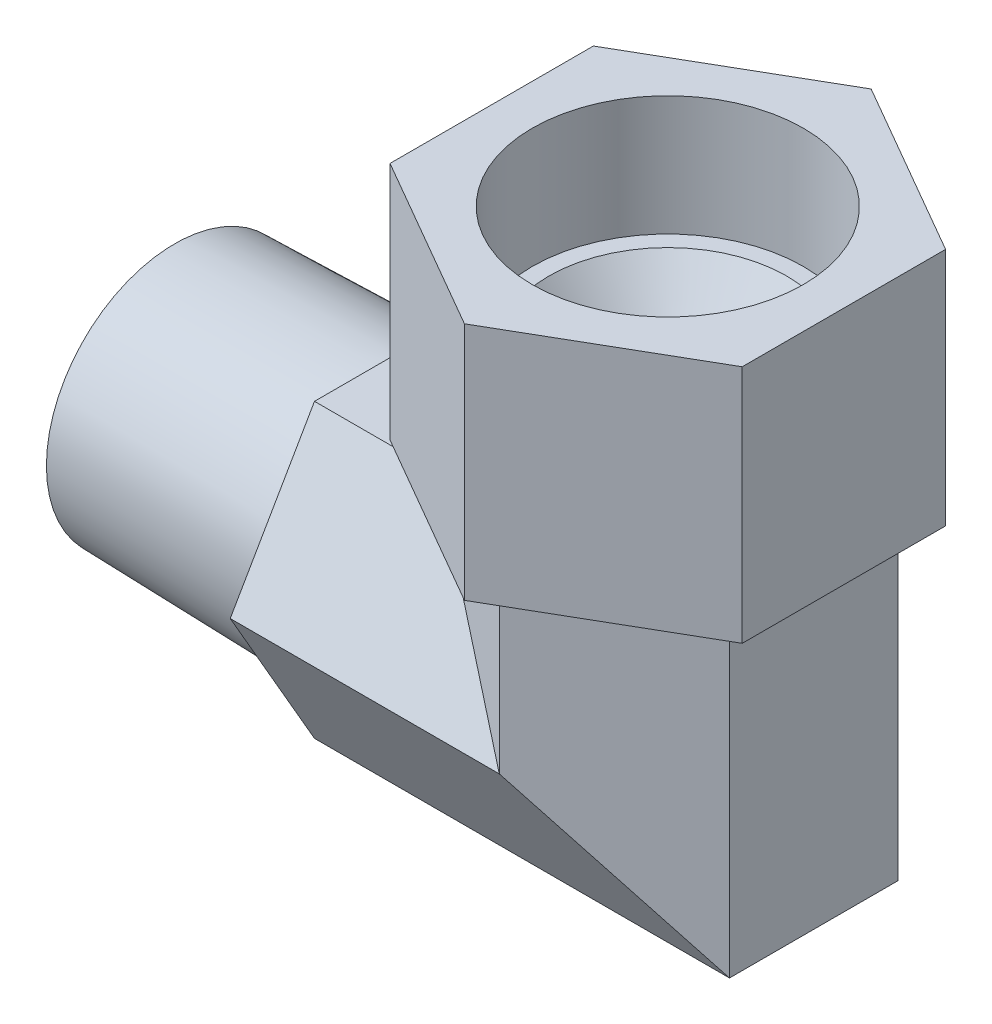
SolidWorks part; units mm, degrees
material "2024-T3"
ref_plane "Front Plane" through (0, 0, 0) normal (0, 0, 1) x (1, 0, 0)
ref_plane "Top Plane" through (0, 0, 0) normal (0, 1, 0) x (1, 0, 0)
ref_plane "Right Plane" through (0, 0, 0) normal (1, 0, 0) x (0, 0, -1)
sketch "Sketch1" plane through (0, 0, 0) normal (0, 0, 1) x (1, 0, 0)
  line L0 (0, 0) -> (33.9096, 0) construction
  line L7 (0, 0) -> (44.45, 0)
  line L8 (44.45, 0) -> (44.45, 25.908)
  dimension "D1" = 44.45
  dimension "D2" = 25.908
ref_plane "Plane1" through (0, 0, 0) normal (1, 0, 0) x (0, 0, -1)
sketch "Sketch2" plane through (0, 0, 0) normal (1, 0, 0) x (0, 0, -1)
  line L0 (0, 0) -> (27.4531, 0) construction
  line L1 (7.5963, 13.1572) -> (-7.5963, 13.1572)
  line L2 (-7.5963, 13.1572) -> (-15.1926, 0)
  line L3 (-15.1926, 0) -> (-7.5963, -13.1572)
  line L4 (-7.5963, -13.1572) -> (7.5963, -13.1572)
  line L5 (7.5963, -13.1572) -> (15.1926, 0)
  line L6 (15.1926, 0) -> (7.5963, 13.1572)
  circle A0 centre (0, 0) radius 13.1572 construction
  dimension "D1" = 26.3144
sweep "Sweep1" add profiles "Sketch2" path "Sketch1"
sketch "Sketch3" plane through (0, 0, 0) normal (-1, 0, 0) x (0, 0, 1)
  circle A0 centre (0, 0) radius 9.1313
  dimension "D1" = 18.2626
extrude "Cut-Extrude1" cut sketch "Sketch3" against normal blind 52.1843
sketch "Sketch4" plane through (0, 25.908, 0) normal (0, 1, 0) x (1, 0, 0)
  line L0 (0, 0) -> (44.45, 0) construction
  line L1 (44.45, 15.1926) -> (44.45, -15.1926) construction
  line L2 (44.45, -15.1926) -> (31.2928, -7.5963) construction
  line L3 (0, -15.1926) -> (44.45, -15.1926) construction
  line L4 (57.6072, 0) -> (31.2928, 0) construction
  line L5 (57.6072, -7.5963) -> (57.6072, 7.5963) construction
  line L6 (31.2928, 7.5963) -> (31.2928, -7.5963) construction
  circle A0 centre (44.45, 0) radius 7.7343
  dimension "D1" = 15.4686
extrude "Cut-Extrude2" cut sketch "Sketch4" against normal blind 25.908
chamfer "Chamfer1" distance 3.9624 angle 37 1 edges at (36.7157, 25.908, 0) first distance on face at (36.7157, 25.908, 0)
sketch "Sketch5" plane through (0, 0, 0) normal (-1, 0, 0) x (0, 0, 1)
  line L6 (-7.5963, 13.1572) -> (-15.1926, 0)
  line L7 (-15.1926, 0) -> (-7.5963, -13.1572)
  line L8 (-7.5963, -13.1572) -> (7.5963, -13.1572)
  line L9 (7.5963, -13.1572) -> (15.1926, 0)
  line L10 (15.1926, 0) -> (7.5963, 13.1572)
  line L11 (7.5963, 13.1572) -> (-7.5963, 13.1572)
  line L12 (-7.5963, 13.1572) -> (-15.1926, 0)
  line L13 (-15.1926, 0) -> (-7.5963, -13.1572)
  line L14 (-7.5963, -13.1572) -> (7.5963, -13.1572)
  line L15 (7.5963, -13.1572) -> (15.1926, 0)
  line L16 (15.1926, 0) -> (7.5963, 13.1572)
  line L17 (7.5963, 13.1572) -> (-7.5963, 13.1572)
  circle A0 centre (0, 0) radius 11.5633
  dimension "D2" = 23.1267
  dimension "D1" = 0
extrude "Cut-Extrude3" cut sketch "Sketch5" against normal blind 20.1981 draft 1.47
sketch "Sketch6" plane through (0, 0, 0) normal (-1, 0, 0) x (0, 0, 1)
  line L0 (-15.1926, 0) -> (-7.5963, 13.1572) construction
  line L1 (-15.1926, 0) -> (-7.5963, 13.1572)
  line L2 (-7.5963, 13.1572) -> (7.5963, 13.1572) construction
  line L3 (-7.5963, 13.1572) -> (7.5963, 13.1572)
  line L4 (7.5963, 13.1572) -> (15.1926, 0) construction
  line L5 (7.5963, 13.1572) -> (15.1926, 0)
  line L6 (15.1926, 0) -> (7.5963, -13.1572) construction
  line L7 (15.1926, 0) -> (7.5963, -13.1572)
  line L8 (7.5963, -13.1572) -> (-7.5963, -13.1572) construction
  line L9 (7.5963, -13.1572) -> (-7.5963, -13.1572)
  line L10 (-7.5963, -13.1572) -> (-15.1926, 0) construction
  line L11 (-7.5963, -13.1572) -> (-15.1926, 0)
  circle A0 centre (0, 0) radius 12.0817 construction
  circle A1 centre (0, 0) radius 12.0817
extrude "Cut-Extrude4" cut sketch "Sketch6" against normal up to surface (20.1981 mm away) up to face at (20.1981, 0, 12.0817)
sketch "Sketch7" plane through (0, 25.908, 0) normal (0, 1, 0) x (1, 0, 0)
  line L0 (57.6072, 7.5963) -> (57.6072, -7.5963) construction
  line L1 (44.45, 18.3309) -> (28.575, 9.1654)
  line L2 (28.575, 9.1654) -> (28.575, -9.1654)
  line L3 (28.575, -9.1654) -> (44.45, -18.3309)
  line L4 (44.45, -18.3309) -> (60.325, -9.1654)
  line L5 (60.325, -9.1654) -> (60.325, 9.1654)
  line L6 (60.325, 9.1654) -> (44.45, 18.3309)
  circle A0 centre (44.45, 0) radius 15.875 construction
  circle A1 centre (44.45, 0) radius 12.2174
  dimension "D2" = 24.4348
  dimension "D1" = 31.75
extrude "Boss-Extrude1" add sketch "Sketch7" along normal mid plane 21.59
